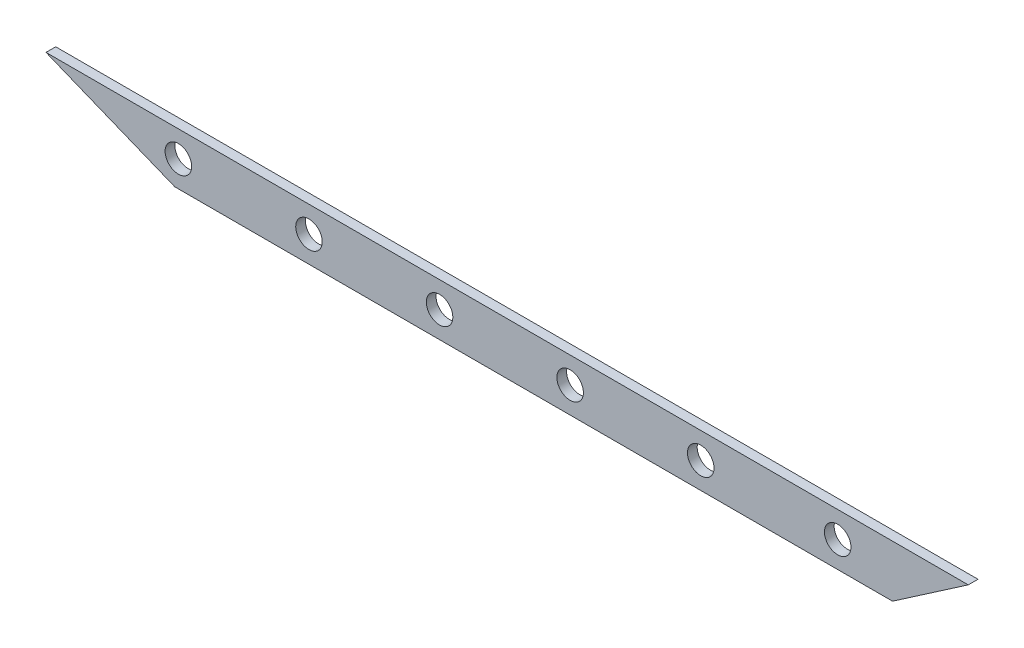
SolidWorks part; units mm, degrees
material "5052-H32"
ref_plane "Front Plane" through (0, 0, 0) normal (0, 0, 1) x (1, 0, 0)
ref_plane "Top Plane" through (0, 0, 0) normal (0, 1, 0) x (1, 0, 0)
ref_plane "Right Plane" through (0, 0, 0) normal (1, 0, 0) x (0, 0, -1)
sketch "Sketch1" plane through (0, 0, 0) normal (0, 0, 1) x (1, 0, 0)
  line L1 (428.1206, 33.3333) -> (428.1206, 28.5708)
  line L3 (428.1206, 28.5708) -> (0, 28.5708)
  line L4 (0, 28.5708) -> (-98.8794, 3.851)
  line L6 (-98.8794, 3.851) -> (-31.8794, -96.649)
  line L7 (428.1206, 28.5708) -> (403.1206, -71.149)
  line L9 (403.1206, -71.149) -> (366, -96.649)
  line L10 (-31.8794, -96.649) -> (366, -96.649)
  circle A0 centre (16, -83.899) radius 6.5
  circle A1 centre (80, -83.899) radius 6.5
  circle A2 centre (144, -83.899) radius 6.5
  circle A3 centre (208, -83.899) radius 6.5
  circle A4 centre (272, -83.899) radius 6.5
  circle A5 centre (339.1206, -83.899) radius 6.5
  point P0 (-48.8794, -71.149)
  point P2 (-31.8794, -96.649)
  point P8 (48, -83.899)
  point P9 (403.1206, -71.149)
  dimension "D2" = 32
  dimension "D4" = 64
  dimension "D1" = 25.5
  dimension "D3" = 75
  dimension "D5" = 25
  dimension "D6" = 64
  dimension "D7" = 527
  dimension "D9" = 64
  dimension "D10" = 64
  dimension "D11" = 64
  dimension "D12" = 123.69
  dimension "D13" = 12.75
extrude "Boss-Extrude1" add sketch "Sketch1" along normal blind 4.7625 contours L3 L4 L6 L10 L9 L7
extrude "Cut-Extrude1" cut sketch "Sketch1<4>" along normal through all contours A0 | A1 | A2 | A3 | A4 | A5 region at (16, -83.899, 0)
sketch "Sketch1<4>" plane through (0, 0, 0) normal (0, 0, 1) x (1, 0, 0) same geometry as "Sketch1"
sketch "Sketch2" plane through (0, 0, 0) normal (0, 0, -1) x (-1, 0, 0)
  circle A0 centre (-307.1206, -83.899) radius 6.5
  circle A2 centre (-249.5603, -111.8778) radius 6.5
  circle A3 centre (-192, -83.899) radius 6.5
  circle A4 centre (-128, -83.899) radius 6.5
  circle A5 centre (-64, -83.899) radius 6.5
  circle A6 centre (0, -83.899) radius 6.5
  dimension "D2" = 0
  dimension "D3" = 64
  dimension "D4" = 64
  dimension "D5" = 64
  dimension "D6" = 64
  dimension "D7" = 64
  dimension "D1" = 32
sketch "Sketch5" plane through (0, 0, 0) normal (0, 0, -1) x (-1, 0, 0)
  line L0 (48.8794, -71.149) -> (-14.2353, -96.649)
  line L1 (31.8794, -96.649) -> (-366, -96.649) construction
  line L2 (-14.2353, -96.649) -> (31.8794, -96.649)
  line L3 (31.8794, -96.649) -> (48.8794, -71.149)
  line L6 (-366, -96.649) -> (-403.1206, -71.149)
  line L7 (-403.1206, -71.149) -> (-352, -71.149)
  line L9 (-352, -71.149) -> (-326.5, -96.649)
  line L11 (-366, -96.649) -> (-326.5, -96.649)
  dimension "D1" = 22
  dimension "D2" = 45
extrude "Cut-Extrude2" [suppressed] cut sketch "Sketch5" against normal up to next
sketch "Sketch6" plane through (0, 0, 4.7625) normal (0, 0, 1) x (1, 0, 0)
  line L0 (-48.8794, -71.149) -> (14.2353, -96.649)
  line L1 (-31.8794, -96.649) -> (366, -96.649) construction
  line L2 (14.2353, -96.649) -> (-31.8794, -96.649)
  line L3 (-31.8794, -96.649) -> (-48.8794, -71.149)
  dimension "D1" = 158
extrude "Cut-Extrude3" cut sketch "Sketch6" against normal blind 10
sketch "Sketch7" plane through (0, 0, 4.7625) normal (0, 0, 1) x (1, 0, 0)
  line L0 (-48.8794, -71.149) -> (403.1206, -71.149)
  line L1 (-48.8794, -71.149) -> (-98.8794, 3.851)
  line L2 (-98.8794, 3.851) -> (0, 28.5708)
  line L3 (0, 28.5708) -> (428.1206, 28.5708)
  line L4 (428.1206, 28.5708) -> (403.1206, -71.149)
extrude "Cut-Extrude4" cut sketch "Sketch7" against normal up to next
